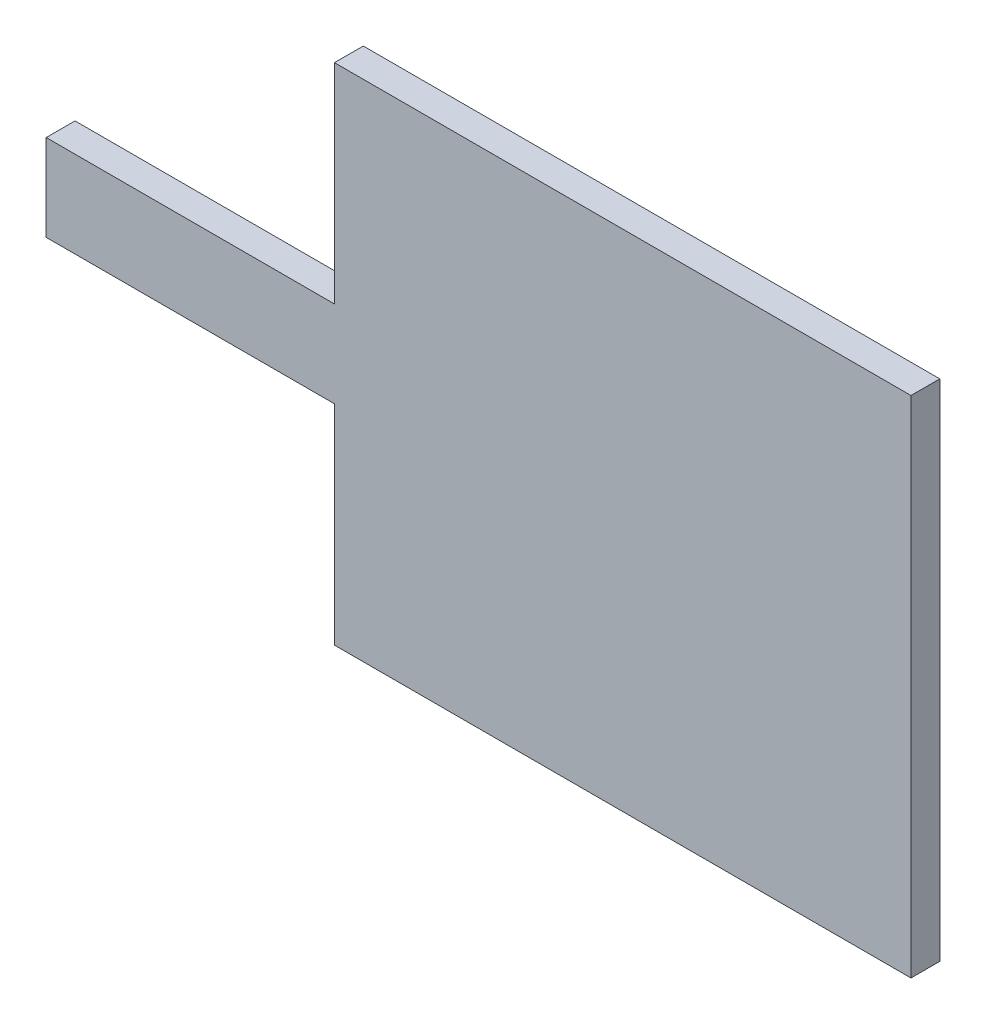
SolidWorks part; units mm, degrees
material "6061-T4 (SS)"
ref_plane "Front Plane" through (0, 0, 0) normal (0, 0, 1) x (1, 0, 0)
ref_plane "Top Plane" through (0, 0, 0) normal (0, 1, 0) x (1, 0, 0)
ref_plane "Right Plane" through (0, 0, 0) normal (1, 0, 0) x (0, 0, -1)
sketch "Sketch1" plane through (0, 0, 0) normal (0, 0, 1) x (1, 0, 0)
  line L0 (0, 10.25) -> (0, 17.5)
  line L1 (0, 0) -> (20, 0)
  line L2 (0, 0) -> (0, 7.25)
  line L3 (0, 17.5) -> (20, 17.5)
  line L4 (20, 0) -> (20, 17.5)
  line L5 (0, 10.25) -> (-10, 10.25)
  line L7 (0, 7.25) -> (-10, 7.25)
  line L8 (-10, 10.25) -> (-10, 7.25)
  line L9 (0, 7.25) -> (0, 10.25) construction
  dimension "D1" = 17.5
  dimension "D2" = 20
  dimension "D3" = 3
  dimension "D4" = 10
extrude "Boss-Extrude1" add sketch "Sketch1" along normal blind 1
